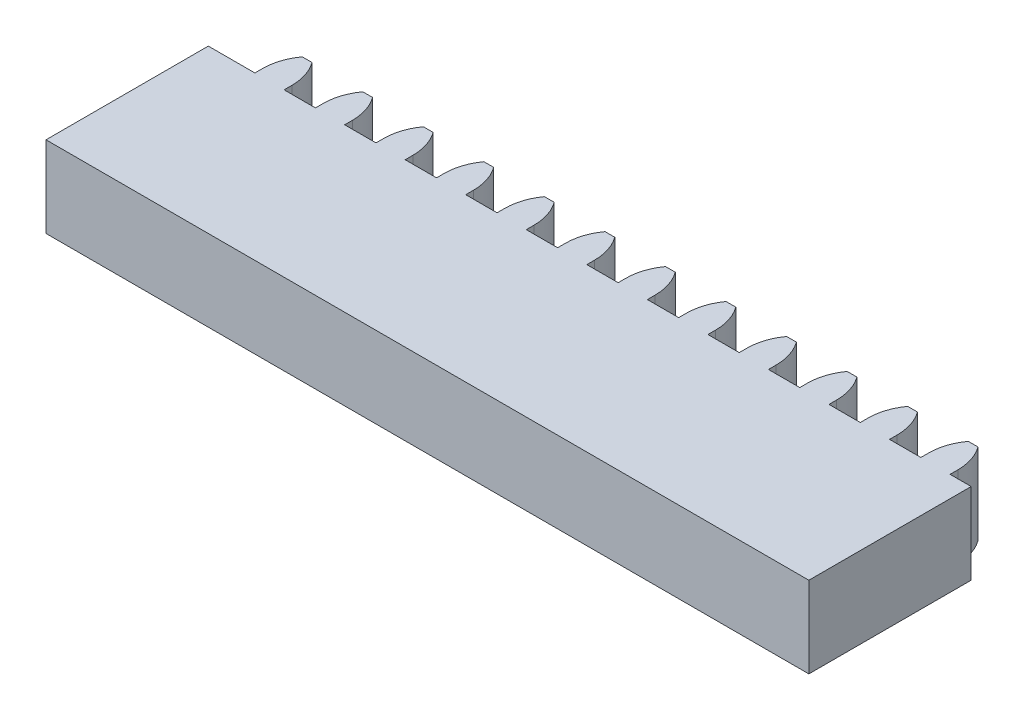
SolidWorks part; units mm, degrees
ref_plane "Front Plane" through (0, 0, 0) normal (0, 0, 1) x (1, 0, 0)
ref_plane "Top Plane" through (0, 0, 0) normal (0, 1, 0) x (1, 0, 0)
ref_plane "Right Plane" through (0, 0, 0) normal (1, 0, 0) x (0, 0, -1)
sketch "Sketch1" plane through (0, 0, 0) normal (0, 1, 0) x (1, 0, 0)
  line L0 (59.69, 12.7) -> (-59.69, 12.7) construction
  line L1 (-59.69, -12.7) -> (59.69, -12.7)
  line L2 (-59.69, -12.7) -> (-59.69, 12.7)
  line L3 (-59.69, 12.7) -> (59.69, 12.7)
  line L4 (59.69, -12.7) -> (59.69, 12.7)
  line L5 (-59.69, -12.7) -> (59.69, 12.7) construction
  line L6 (-59.69, 12.7) -> (59.69, -12.7) construction
  line L9 (55.4388, 18.5953) -> (54.102, 18.5953) construction
  line L10 (54.102, 19.8421) -> (54.102, 12.7) construction
  line L11 (56.8049, 12.7) -> (51.3991, 12.7) construction
  line L12 (56.6937, 16.3642) -> (54.102, 16.3642) construction
  line L13 (54.102, 12.7) -> (54.102, 22.2227) construction
  line L14 (51.054, 13.8556) -> (51.054, 12.7) construction
  line L15 (55.4388, 18.5953) -> (52.7652, 18.5953) construction
  line L16 (57.15, 13.8556) -> (57.15, 12.7) construction
  line L17 (51.816, 12.7) -> (51.816, 13.9083)
  line L18 (56.388, 12.7) -> (56.388, 13.9083)
  line L19 (53.34, 18.5953) -> (54.864, 18.5953)
  line L20 (57.15, 13.8556) -> (54.102, 13.8556) construction
  arc A2 (52.7652, 18.5953) -> (51.054, 13.8556) centre (58.4734, 13.8556) ccw construction
  arc A3 (55.4388, 18.5953) -> (57.15, 13.8556) centre (49.7306, 13.8556) cw construction
  arc A4 (51.816, 13.9083) -> (53.34, 18.5953) centre (59.7852, 13.9083) cw
  arc A5 (56.388, 13.9083) -> (54.864, 18.5953) centre (48.4188, 13.9083) ccw
  point P0 (0, 0)
  point P20 (59.8284, 19.8421)
  point P21 (54.102, 19.8421)
  dimension "D9" = 4.687
  dimension "D10" = 1.524
  dimension "D8" = 7.4194
  dimension "D1" = 25.4
  dimension "D2" = 119.38
  dimension "D3" = 5.588
  dimension "D4" = 4.572
  dimension "D5" = 5.4057
  dimension "D6" = 5.8953
  dimension "D7" = 2.54
extrude "Boss-Extrude1" add sketch "Sketch1" along normal blind 12.7 contours L1 L4 L3 L2 region at (0, 0, 0)
extrude "Boss-Extrude2" add sketch "Sketch1<4>" along normal blind 12.7 contours A3 L15 A2 L14 L3 L16 region at (54.102, 0, -15.2809)
sketch "Sketch1<4>" plane through (0, 0, 0) normal (0, 1, 0) x (1, 0, 0) same geometry as "Sketch1"
pattern_linear "LPattern1" count 12 spacing 9.4742 along (-1, 0, 0) of "Boss-Extrude2"
